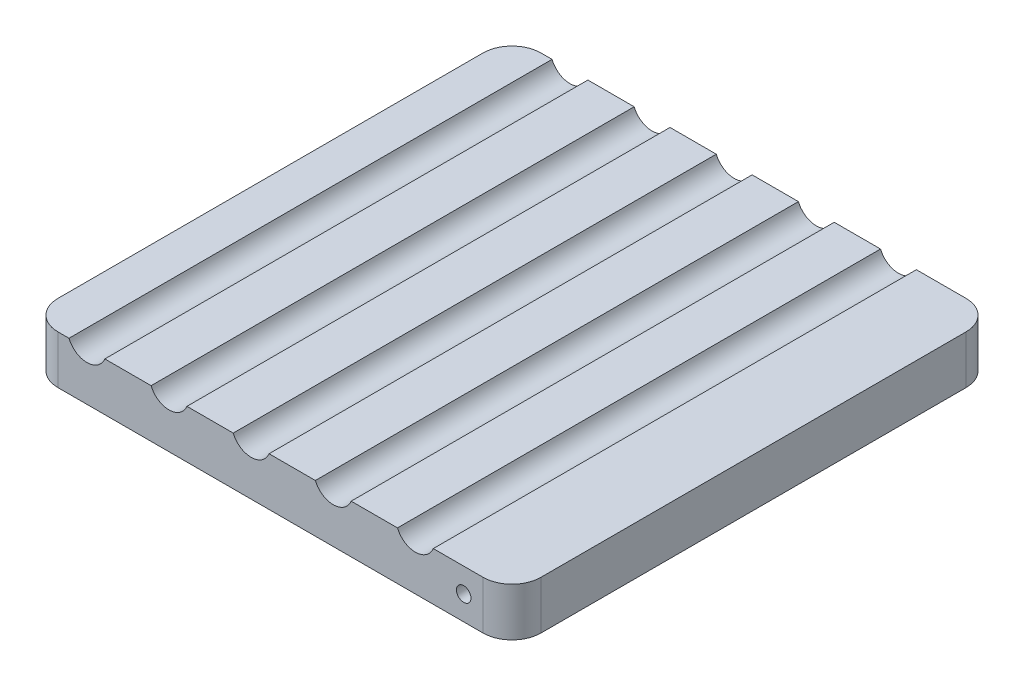
SolidWorks part; units mm, degrees
material "1350 Alloy"
ref_plane "Front Plane" through (0, 0, 0) normal (0, 0, 1) x (1, 0, 0)
ref_plane "Top Plane" through (0, 0, 0) normal (0, 1, 0) x (1, 0, 0)
ref_plane "Right Plane" through (0, 0, 0) normal (1, 0, 0) x (0, 0, -1)
sketch "Sketch2" plane through (0, 0, 0) normal (0, 1, 0) x (1, 0, 0)
  line L1 (-63.5, -63.5) -> (63.5, -63.5)
  line L2 (-63.5, -63.5) -> (-63.5, 63.5)
  line L3 (-63.5, 63.5) -> (63.5, 63.5)
  line L4 (63.5, -63.5) -> (63.5, 63.5)
  point P0 (0, 0)
  point P6 (0, 63.5)
  point P7 (63.5, 0)
  dimension "D1" = 127
  dimension "D2" = 127
extrude "Boss-Extrude1" add sketch "Sketch2" along normal blind 12.7
fillet "Fillet1" radius 7.62 4 edges at (-63.5, 6.35, -63.5) (-63.5, 6.35, 63.5) (63.5, 6.35, -63.5) (63.5, 6.35, 63.5)
sketch "Sketch3" plane through (0, 0, 63.5) normal (0, 0, 1) x (1, 0, 0)
  line L0 (63.5, 12.7) -> (63.5, 0) construction
  line L1 (-55.88, 0) -> (55.88, 0) construction
  line L2 (-55.88, 12.7) -> (55.88, 12.7) construction
  circle A0 centre (50.8, 6.35) radius 1.905
  circle A1 centre (38.1, 14.605) radius 5.08
  dimension "D1" = 3.81
  dimension "D5" = 10.16
  dimension "D2" = 12.7
  dimension "D3" = 6.35
  dimension "D4" = 25.4
  dimension "D6" = 1.905
extrude "Cut-Extrude1" cut sketch "Sketch3" against normal through all contours A1
pattern_linear "LPattern1" count 5 spacing 21.59 along (-1, 0, 0) of "Cut-Extrude1"
extrude "Cut-Extrude2" cut sketch "Sketch3<3>" against normal through all
sketch "Sketch3<3>" plane through (0, 0, 63.5) normal (0, 0, 1) x (1, 0, 0) same geometry as "Sketch3"
